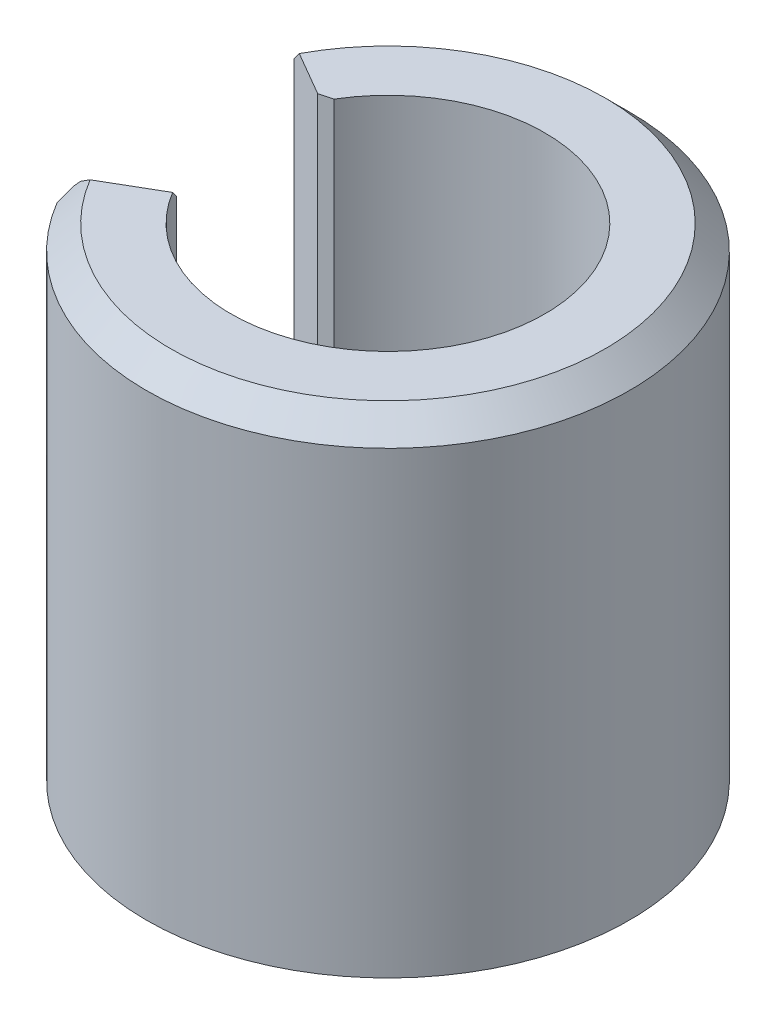
SolidWorks part; units mm, degrees
ref_plane "Front Plane" through (0, 0, 0) normal (0, 0, 1) x (1, 0, 0)
ref_plane "Top Plane" through (0, 0, 0) normal (0, 1, 0) x (1, 0, 0)
ref_plane "Right Plane" through (0, 0, 0) normal (1, 0, 0) x (0, 0, -1)
sketch "Sketch1" plane through (0, 0, 0) normal (0, 1, 0) x (1, 0, 0)
  line L0 (-4.3974, 2.3797) -> (-2.8831, 1.5)
  line L1 (-4.3974, -2.3797) -> (-2.8831, -1.5)
  line L2 (0, 0) -> (-11.0056, 0) construction
  circle A0 centre (0, 0) radius 5
  circle A1 centre (0, 0) radius 3.25
  dimension "D1" = 6.5
  dimension "D2" = 10
  dimension "D3" = 3
  dimension "D4" = 60.312
extrude "Boss-Extrude1" add sketch "Sketch1" along normal blind 10 contours A1 L1 A0 L0 region at (1.1937, 0, -4.714)
chamfer "Chamfer1" distance 0.2 angle 45 4 edges at (-3.6403, 10, 1.9399) (-4.3974, 5, 2.3797) (-4.3974, 5, -2.3797) (-2.8831, 5, -1.5) first distance on face at (-3.6403, 5, 1.9399) first distance on face at (0.3013, 5, 0) first distance on face at (-3.6403, 5, -1.9399)
chamfer "Chamfer2" distance 0.5 angle 45 1 edges at (5, 10, -0.0029)
